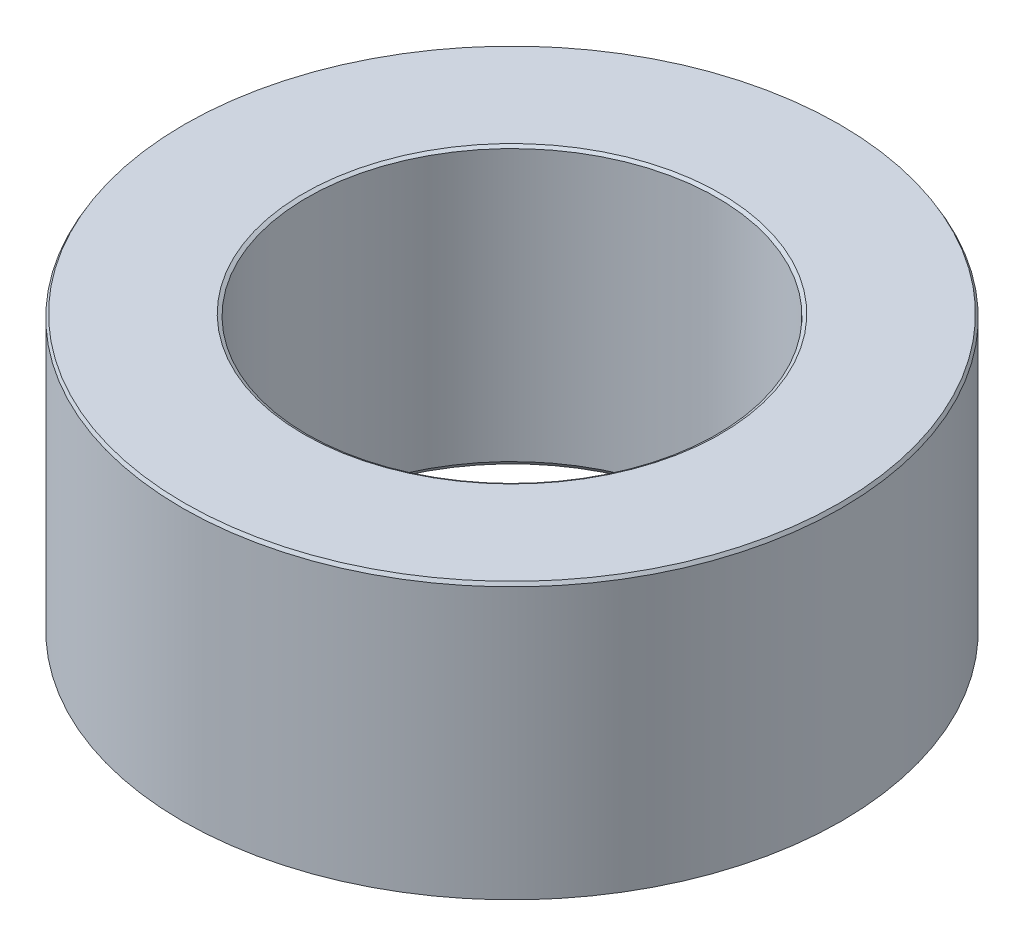
SolidWorks part; units mm, degrees
ref_plane "Front Plane" through (0, 0, 0) normal (0, 0, 1) x (1, 0, 0)
ref_plane "Top Plane" through (0, 0, 0) normal (0, 1, 0) x (1, 0, 0)
ref_plane "Right Plane" through (0, 0, 0) normal (1, 0, 0) x (0, 0, -1)
sketch "Sketch1" plane through (0, 0, 0) normal (0, 1, 0) x (1, 0, 0)
  circle A0 centre (0, 0) radius 37.5
  dimension "SLEEVE_OD" = 75
extrude "Boss-Extrude1" add sketch "Sketch1" along normal blind 31.4396
sketch "Sketch2" plane through (0, 0, 0) normal (0, 1, 0) x (1, 0, 0)
  circle A0 centre (0, 0) radius 23.3243
  dimension "BORE_D" = 46.6486
extrude "Cut-Extrude1" cut sketch "Sketch2" along normal through all
chamfer "Chamfer1" distance 0.3856 angle 30 4 edges at (0, 31.4396, 23.3243) (0, 0, 23.3243) (0, 0, 37.5) (0, 31.4396, 37.5) first distance on face at (0, 31.4396, 23.3243) first distance on face at (0, 0, 23.3243) first distance on face at (0, 31.4396, 37.5)
